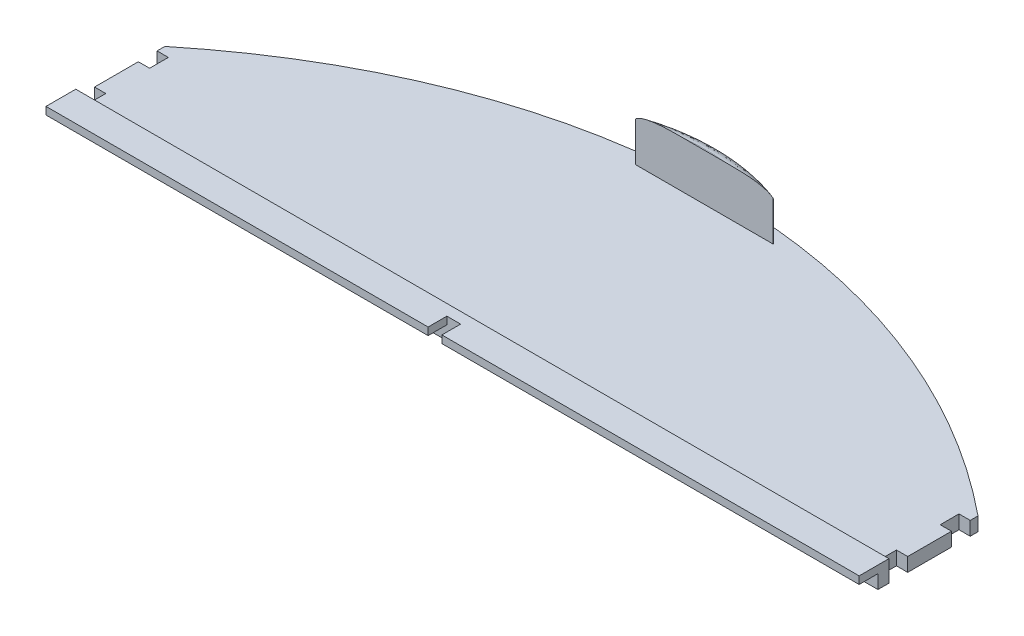
SolidWorks part; units mm, degrees
ref_plane "Front Plane" through (0, 0, 0) normal (0, 0, 1) x (1, 0, 0)
ref_plane "Top Plane" through (0, 0, 0) normal (0, 1, 0) x (1, 0, 0)
ref_plane "Right Plane" through (0, 0, 0) normal (1, 0, 0) x (0, 0, -1)
sketch "Sketch2" plane through (0, 0, 0) normal (0, 1, 0) x (1, 0, 0)
  line L0 (0, 0) -> (130, 0)
  line L1 (130, 0) -> (130, 16)
  line L2 (0, 0) -> (0, 16)
  conic Q0 (0, 16) -> (130, 16) control (65, 68.961) rho 0.453164
  point P6 (65, 0)
  dimension "D1" = 130
  dimension "D2" = 16
  dimension "D3" = 40
extrude "Boss-Extrude1" add sketch "Sketch2" along normal blind 2.2
ref_plane "Plane1" through (0, 2.2, 0) normal (0, 1, 0) x (1, 0, 0)
sketch "Sketch3" plane through (0, 2.2, 0) normal (0, 1, 0) x (1, 0, 0)
  line L0 (0, 1.76) -> (130, 1.76)
  line L1 (0, 16) -> (0, 0) construction
  line L2 (130, 0) -> (130, 16) construction
  line L3 (130, 1.76) -> (130, -3)
  line L4 (130, -3) -> (63.2884, -3)
  line L5 (0, -3) -> (0, 1.76)
  line L6 (61.0884, -3) -> (61.0884, 0)
  line L7 (0, 0) -> (130, 0) construction
  line L8 (61.0884, 0) -> (63.2884, 0)
  line L9 (63.2884, 0) -> (63.2884, -3)
  line L10 (61.0884, -3) -> (0, -3)
  dimension "D1" = 1.76
  dimension "D2" = 4.76
  dimension "D3" = 2.2
extrude "Boss-Extrude2" add sketch "Sketch3" along normal blind 1.2
sketch "Sketch4" plane through (0, 2.2, 0) normal (0, 1, 0) x (1, 0, 0)
  line L0 (54, 37.26) -> (76, 37.26)
  line L1 (76, 37.26) -> (76, 37.46)
  line L2 (54, 37.26) -> (54, 37.46)
  line L3 (130, 1.76) -> (0, 1.76) construction
  conic Q0 (54, 37.46) -> (76, 37.46) control (65, 41.8734) rho 0.453164
  point P9 (65, 1.76)
  dimension "D2" = 0.2
  dimension "D3" = 22
  dimension "D4" = 35.5
  dimension "D5" = 2.2
extrude "Boss-Extrude3" add sketch "Sketch4" along normal blind 7.5
fillet "Fillet1" radius 1 2 edges at (76, 5.95, -37.46) (54, 5.95, -37.46)
fillet "Fillet2" radius 2 1 edges
ref_plane "Plane2" through (0, 0, 0) normal (-1, 0, 0) x (0, 0, 1)
ref_plane "Plane3" through (130, 0, 0) normal (1, 0, 0) x (0, 0, -1)
sketch "Sketch5" plane through (130, 0, 0) normal (1, 0, 0) x (0, 0, -1)
  line L0 (36.9605, 2.2) -> (-36.9605, 2.2) construction
  line L1 (1.76, 2.2) -> (4.76, 2.2)
  line L2 (1.76, 2.2) -> (1.76, 0)
  line L3 (1.76, 0) -> (4.76, 0)
  line L4 (4.76, 2.2) -> (4.76, 0)
  line L5 (0, 0) -> (16, 0) construction
  line L6 (1.76, 3.4) -> (1.76, 2.2) construction
  line L8 (11.76, 2.2) -> (14.76, 2.2)
  line L9 (11.76, 2.2) -> (11.76, 0)
  line L10 (11.76, 0) -> (14.76, 0)
  line L11 (14.76, 2.2) -> (14.76, 0)
  dimension "D1" = 0
  dimension "D2" = 3
  dimension "D3" = 3
  dimension "D4" = 7
extrude "Cut-Extrude1" cut sketch "Sketch5" against normal blind 1.8
sketch "Sketch6" plane through (0, 0, 0) normal (-1, 0, 0) x (0, 0, 1)
  line L0 (-16, 2.2) -> (-1.76, 2.2) construction
  line L1 (-1.76, 2.2) -> (-4.76, 2.2)
  line L2 (-1.76, 2.2) -> (-1.76, 0)
  line L3 (-1.76, 0) -> (-4.76, 0)
  line L4 (-4.76, 2.2) -> (-4.76, 0)
  line L5 (-16, 0) -> (0, 0) construction
  line L7 (-11.76, 2.2) -> (-14.76, 2.2)
  line L8 (-11.76, 2.2) -> (-11.76, 0)
  line L9 (-11.76, 0) -> (-14.76, 0)
  line L10 (-14.76, 2.2) -> (-14.76, 0)
  dimension "D1" = 0
  dimension "D2" = 3
  dimension "D3" = 3
  dimension "D4" = 7
extrude "Cut-Extrude2" cut sketch "Sketch6" against normal blind 1.8
